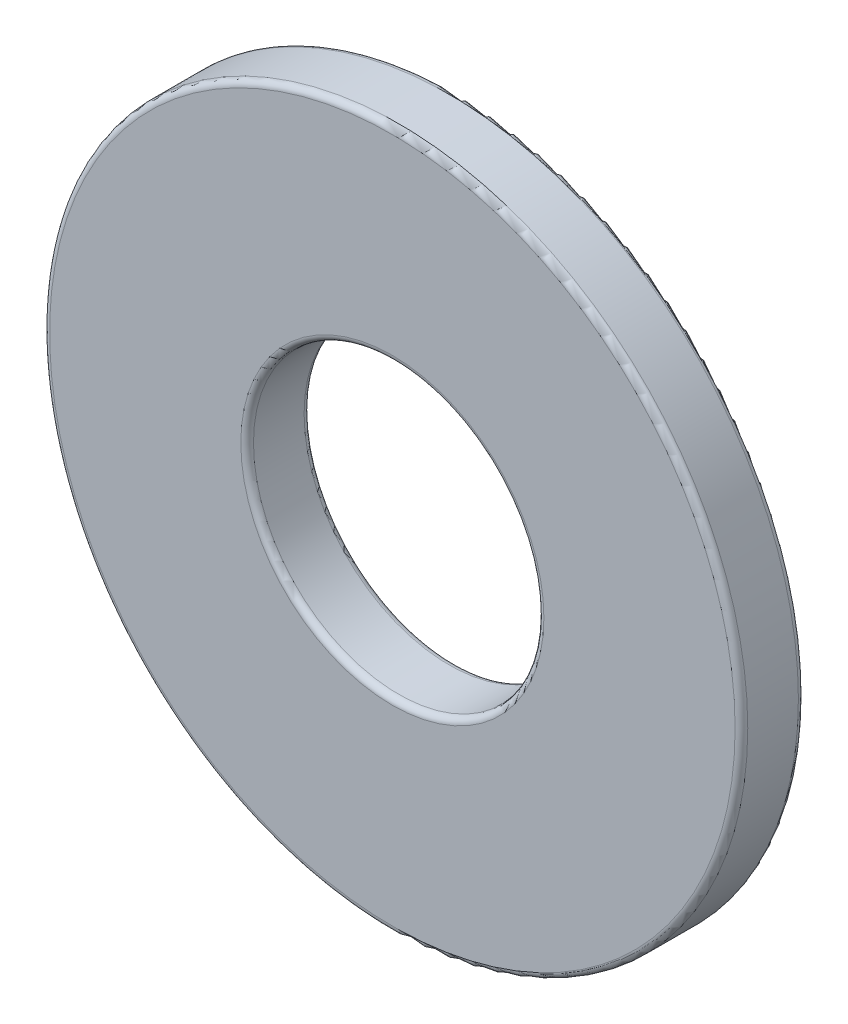
SolidWorks part; units mm, degrees
ref_plane "Front Plane" through (0, 0, 0) normal (0, 0, 1) x (1, 0, 0)
ref_plane "Top Plane" through (0, 0, 0) normal (0, 1, 0) x (1, 0, 0)
ref_plane "Right Plane" through (0, 0, 0) normal (1, 0, 0) x (0, 0, -1)
sketch "Sketch1" plane through (0, 0, 0) normal (0, 0, 1) x (1, 0, 0)
  circle A0 centre (0, 0) radius 9.525 construction
  circle A1 centre (0, 0) radius 3.9624 construction
  dimension "OD" = 19.05
  dimension "ID" = 7.9248
sketch "Sketch2" plane through (0, 0, 0) normal (1, 0, 0) x (0, 0, -1)
  line L0 (-0.8636, -9.525) -> (0.8636, -9.525) construction
  point P0 (0.6096, -9.525)
  point P4 (0, -9.525)
  dimension "Thickness Max" = 1.7272
  dimension "Thickness Min" = 1.4732
sketch "Sketch3" plane through (0, 0, 0) normal (0, 0, 1) x (1, 0, 0)
  circle A0 centre (0, 0) radius 9.525 construction
  circle A1 centre (0, 0) radius 9.525
  circle A2 centre (0, 0) radius 3.9624 construction
  circle A3 centre (0, 0) radius 3.9624
extrude "Boss-Extrude1" add sketch "Sketch3" against normal up to vertex (0.8636 mm away) and the other way up to vertex (0.8636 mm away) up to point (0, -9.525, -0.8636) other way up to point (0, -9.525, 0.8636)
fillet "Fillet1" radius 0.1727 4 edges at (9.525, 0, -0.8636) (3.9624, 0, -0.8636) (3.9624, 0, 0.8636) (9.525, 0, 0.8636)
equation "\"D1@Fillet1\" = \"Thickness Max@Sketch2\" * 0.1"
